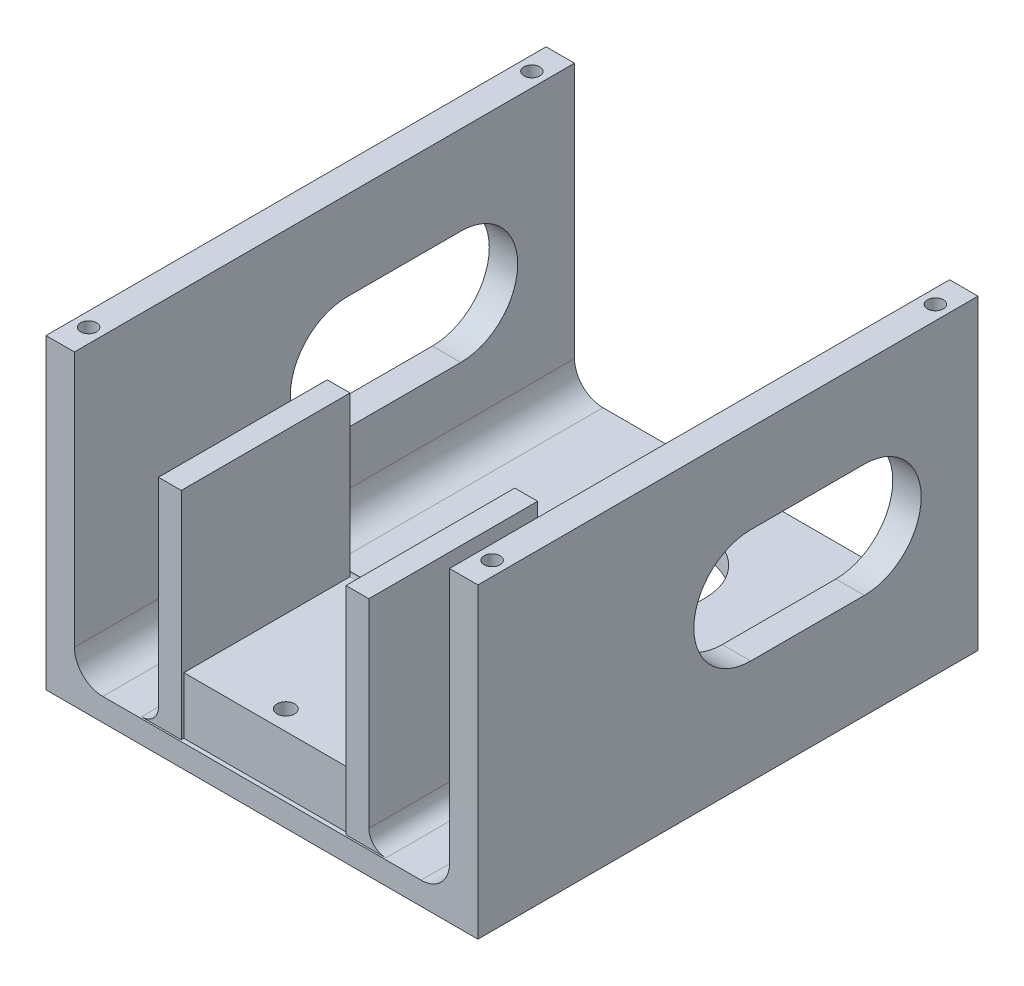
SolidWorks part; units mm, degrees
ref_plane "前视基准面" through (0, 0, 0) normal (0, 0, 1) x (1, 0, 0)
ref_plane "上视基准面" through (0, 0, 0) normal (0, 1, 0) x (1, 0, 0)
ref_plane "右视基准面" through (0, 0, 0) normal (1, 0, 0) x (0, 0, -1)
sketch "草图4" plane through (0, -14.4, 0) normal (0, -1, 0) x (1, 0, 0)
  circle A0 centre (-10, 2.1) radius 1.55
  circle A1 centre (10, 2.1) radius 1.55
sketch "草图5" plane through (0, -14.4, 0) normal (0, -1, 0) x (1, 0, 0)
  circle A0 centre (0, 25.8) radius 1.55
sketch "草图6" plane through (0, -14.4, 0) normal (0, -1, 0) x (1, 0, 0)
  line L0 (-14.4921, 29.7026) -> (-14.4988, 28.8) construction
  line L1 (-14.4954, 29.2513) -> (14.4974, 29.2513)
  line L2 (-14.4954, 29.2513) -> (-14.4954, 0.3)
  line L3 (-14.4954, 0.3) -> (14.4974, 0.3)
  line L4 (14.4974, 29.2513) -> (14.4974, 0.3)
extrude "凸台-拉伸2" add sketch "草图6" along normal blind 10
sketch "草图8" plane through (0, -24.4, 0) normal (0, -1, 0) x (1, 0, 0)
  line L6 (-38, 30) -> (38, 30)
  line L7 (-38, 30) -> (-38, -58)
  line L8 (-38, -58) -> (38, -58)
  line L9 (38, 30) -> (38, -58)
extrude "凸台-拉伸3" add sketch "草图8" along normal blind 4
extrude "切除-拉伸2" cut sketch "草图4" along normal blind 15
extrude "切除-拉伸3" cut sketch "草图5" along normal blind 15
sketch "草图10" plane through (0, -24.4, 0) normal (0, 1, 0) x (1, 0, 0)
  line L1 (14.4921, -29.7026) -> (18.5147, -29.7026)
  line L2 (14.4921, -29.7026) -> (14.4921, 0)
  line L3 (14.4921, 0) -> (18.5147, 0)
  line L4 (18.5147, -29.7026) -> (18.5147, 0)
extrude "凸台-拉伸9" add sketch "草图10" along normal blind 38
sketch "草图11" plane through (0, -24.4, 0) normal (0, 1, 0) x (1, 0, 0)
  line L1 (-14.4921, -29.7026) -> (-18.5023, -29.7026)
  line L2 (-14.4921, -29.7026) -> (-14.4921, 0)
  line L3 (-14.4921, 0) -> (-18.5023, 0)
  line L4 (-18.5023, -29.7026) -> (-18.5023, 0)
extrude "凸台-拉伸10" add sketch "草图11" along normal blind 38
sketch "草图14" plane through (0, -24.4, 0) normal (0, 1, 0) x (1, 0, 0)
  line L1 (-38, 58) -> (-33, 58)
  line L2 (-38, 58) -> (-38, -30)
  line L3 (-38, -30) -> (-33, -30)
  line L4 (-33, 58) -> (-33, -30)
  line L5 (38, -30) -> (-38, -30) construction
  dimension "D1" = 88
  dimension "D2" = 5
extrude "凸台-拉伸14" add sketch "草图14" along normal blind 50
sketch "草图15" plane through (0, -24.4, 0) normal (0, 1, 0) x (1, 0, 0)
  line L1 (38, 58) -> (33, 58)
  line L2 (38, 58) -> (38, -30)
  line L3 (38, -30) -> (33, -30)
  line L4 (33, 58) -> (33, -30)
  line L5 (38, -30) -> (-33, -30) construction
  dimension "D1" = 88
  dimension "D2" = 5
extrude "凸台-拉伸15" add sketch "草图15" along normal blind 50
sketch "草图18" plane through (0, -28.4, 0) normal (0, -1, 0) x (1, 0, 0)
  circle A0 centre (0, 25.8) radius 2.5985
sketch "草图19" plane through (0, -28.4, 0) normal (0, -1, 0) x (1, 0, 0)
  circle A0 centre (-10, 2.1) radius 2.6
  circle A1 centre (10, 2.1) radius 2.6
  dimension "D1" = 5.2
  dimension "D2" = 5.2
extrude "切除-拉伸5" cut sketch "草图19" against normal blind 3
extrude "切除-拉伸6" cut sketch "草图18" against normal blind 3 contours A0
sketch "草图21" plane through (0, 25.6, 0) normal (0, 1, 0) x (1, 0, 0)
  circle A0 centre (-35.5, 53) radius 1.4
  circle A1 centre (-35.5, -25) radius 1.4
  circle A2 centre (35.5, 53) radius 1.4
  circle A3 centre (35.5, -25) radius 1.4
extrude "切除-拉伸8" cut sketch "草图21" against normal blind 8
sketch "草图22" plane through (-38, 0, 0) normal (-1, 0, 0) x (0, 0, 1)
  line L3 (-38, 0) -> (-18, 0) construction
  line L5 (-38, 10) -> (-18, 10)
  line L6 (-38, -10) -> (-18, -10)
  arc A0 (-38, 10) -> (-38, -10) centre (-38, 0) ccw
  arc A1 (-18, -10) -> (-18, 10) centre (-18, 0) ccw
  point P9 (-28, 0)
extrude "切除-拉伸9" cut sketch "草图22" against normal blind 80
sketch "草图23" plane through (0, -24.4, 0) normal (0, 1, 0) x (1, 0, 0)
  line L4 (0, 38) -> (0, 18) construction
  line L6 (10, 38) -> (10, 18)
  line L7 (-10, 38) -> (-10, 18)
  arc A0 (10, 38) -> (-10, 38) centre (0, 38) ccw
  arc A1 (-10, 18) -> (10, 18) centre (0, 18) ccw
  point P10 (0, 28)
extrude "切除-拉伸11" cut sketch "草图23" against normal blind 80
fillet "圆角1" radius 5 1 edges at (-33, -24.4, -14) type face fillet first side face at (-33, 0, -28) second side face at (0, -24.4, -28)
fillet "圆角2" radius 5 1 edges at (33, -24.4, -14) type face fillet first side face at (33, 0, -28) second side face at (0, -24.4, -28)
sketch "草图24" plane through (0, -24.4, 0) normal (0, 1, 0) x (1, 0, 0)
  line L1 (-14.4921, -0.3) -> (14.4921, -0.3)
  line L6 (-14.4921, -0.3) -> (-14.4921, 0)
  line L7 (-14.4921, 0) -> (14.4921, 0)
  line L8 (14.4921, -0.3) -> (14.4921, 0)
extrude "凸台-拉伸16" add sketch "草图24" along normal blind 10
sketch "草图25" plane through (0, -24.4, 0) normal (0, 1, 0) x (1, 0, 0)
  line L1 (-18.5023, 0) -> (18.5147, 0)
  line L2 (-18.5023, 0) -> (-18.5023, 2)
  line L3 (-18.5023, 2) -> (18.5147, 2)
  line L4 (18.5147, 0) -> (18.5147, 2)
  dimension "D1" = 2
extrude "凸台-拉伸18" add sketch "草图25" along normal blind 10
fillet "圆角7" radius 2 1 edges at (0.0062, -14.4, -2) type face fillet first side face at (0, -14.4, 24.25) second side face at (0.0062, -19.4, -2)
fillet "圆角8" radius 3 1 edges at (18.5147, -24.4, 13.8513) type face fillet first side face at (18.5147, -8.6643, 9.1652) second side face at (0, -24.4, -28)
fillet "圆角9" radius 3 1 edges at (1.5062, -24.4, -2) type face fillet first side face at (4.1836, -20.7243, -2) second side face at (0, -24.4, -28)
fillet "圆角10" radius 3 1 edges at (-18.5023, -24.4, 12.3513) type face fillet first side face at (-18.5023, -10.5724, 7.2303) second side face at (0, -24.4, -28)
